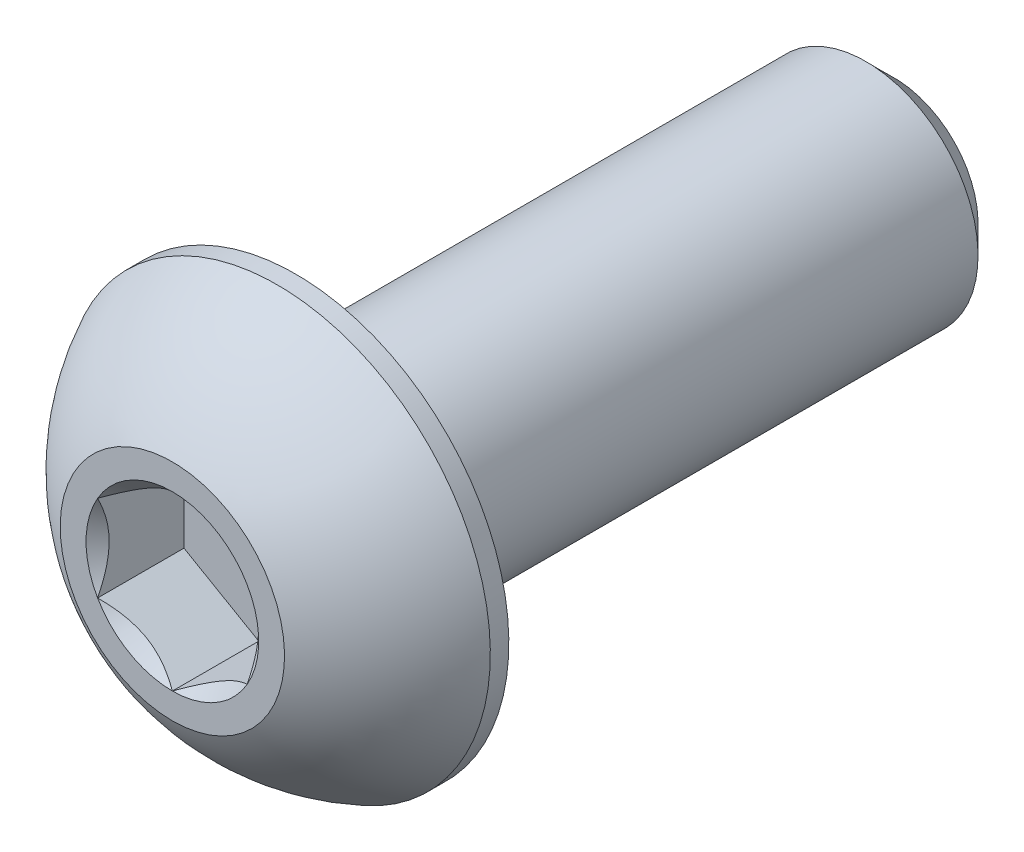
SolidWorks part; units mm, degrees
ref_plane "Front" through (0, 0, 0) normal (0, 0, 1) x (1, 0, 0)
ref_plane "Top" through (0, 0, 0) normal (0, 1, 0) x (1, 0, 0)
ref_plane "Right" through (0, 0, 0) normal (1, 0, 0) x (0, 0, -1)
sketch "Sketch1" plane through (0, 0, 0) normal (1, 0, 0) x (0, 0, -1)
  line L2 (-4, 1.5) -> (4, 1.5)
  line L3 (4, 1.5) -> (4, 0)
  line L4 (4, 0) -> (-4, 0)
  line L6 (-4.2475, 2.85) -> (-4, 2.85) construction
  line L7 (4, 1.5) -> (4, -1.5) construction
  line L8 (-5.65, 0) -> (-4, 0) construction
  line L9 (-4, 2.85) -> (-4, -2.85) construction
  line L11 (-4, 1.5) -> (-4, 0)
  line L13 (-5.65, 1) -> (-5.65, -1) construction
  line L14 (-5.65, 1) -> (-5.65, 1.5) construction
  line L15 (3.9688, 1.5541) -> (4.2188, 1.1211) construction
  line L16 (4.2188, 1.1211) -> (4.4688, 1.5541) construction
  line L17 (4.4688, 1.5541) -> (3.9688, 1.5541) construction
  line L18 (4, 1.5) -> (4.4375, 1.5) construction
  line L19 (4.2188, 1.5541) -> (4.2188, 1.5) construction
  line L20 (4.2188, 1.5) -> (4.2188, 1.1752) construction
  line L21 (4.2188, 1.1752) -> (4.2188, 1.1211) construction
  line L22 (4.1875, 1.1752) -> (4.25, 1.1752)
  line L23 (3.9844, 1.5271) -> (4.4531, 1.5271)
  line L24 (4.25, 1.1752) -> (4.4531, 1.5271)
  line L25 (4.1875, 1.1752) -> (3.9844, 1.5271)
  line L26 (3.625, 1.5) -> (4, 1.125)
  arc A3 (-5.65, 1.5) -> (-4.2475, 2.85) centre (-2.8552, 0) cw construction
  point P29 (4.2187, 1.5271)
  point P30 (2.75, -1.5)
  point P33 (0, 0)
  dimension "Thread Size" = 3
  dimension "D1" = 0.2475
  dimension "Head Height" = 1.65
  dimension "Head Diameter" = 5.7
  dimension "Length" = 8
  dimension "Drive Size" = 2
  dimension "Thread Pitch" = 0.5
  dimension "D3" = 0.0625
  dimension "D2" = 0.375
  dimension "D4" = 45
  dimension "D5" = 1.25
sketch "Sketch10" plane through (0, 0, 0) normal (1, 0, 0) x (0, 0, -1)
  line L0 (3.625, 1.5) -> (4, 1.125) construction
  line L1 (3.625, 1.5) -> (4, 1.125)
  line L4 (4, 1.5) -> (-4, 1.5)
  line L5 (4, 0) -> (4, 1.5)
  line L6 (-4, 0) -> (4, 0)
  line L7 (-4, 1.5) -> (-4, 0)
  line L8 (3.625, 1.5) -> (-4, 1.5)
  line L9 (4, 0) -> (4, 1.125)
  line L10 (-4, 0) -> (4, 0)
  line L11 (-4, 1.5) -> (-4, 0)
  dimension "D1" = 0
revolve "Revolve3" add sketch "Sketch10" angle 360 about L8
sketch "Sketch7" plane through (0, 0, 0) normal (1, 0, 0) x (0, 0, -1)
  line L6 (-4.2475, 2.85) -> (-4, 2.85) construction
  line L8 (-5.65, 0) -> (-4, 0) construction
  line L11 (-4, 2.85) -> (-4, -2.85) construction
  line L12 (-4.2475, 2.85) -> (-4, 2.85)
  line L13 (-5.65, 0) -> (-4, 0)
  line L14 (-5.65, 1) -> (-5.65, -1) construction
  line L15 (-4, 2.85) -> (-4, 0)
  line L16 (-5.65, 1.5) -> (-5.65, 0)
  arc A2 (-4.2475, 2.85) -> (-5.65, 1.5) centre (-2.8552, 0) ccw construction
  arc A3 (-4.2475, 2.85) -> (-5.65, 1.5) centre (-2.8552, 0) ccw
revolve "Revolve2" add sketch "Sketch7" angle 360 mid plane about L13
sketch "Sketch5" plane through (0, 0, 5.65) normal (0, 0, 1) x (1, 0, 0)
  line L1 (1, -0.5774) -> (1, 0.5774)
  line L2 (1, 0.5774) -> (0, 1.1547)
  line L3 (0, 1.1547) -> (-1, 0.5774)
  line L4 (-1, 0.5774) -> (-1, -0.5774)
  line L5 (-1, -0.5774) -> (0, -1.1547)
  line L6 (0, -1.1547) -> (1, -0.5774)
  circle A0 centre (0, 0) radius 1 construction
extrude "Cut-Extrude2" cut sketch "Sketch5" against normal blind 1.155
sketch "Sketch6" plane through (0, 0, 5.65) normal (0, 0, 1) x (1, 0, 0)
  circle A0 centre (0, 0) radius 1.1547
extrude "Cut-Extrude3" cut sketch "Sketch6" against normal blind 1.155 draft 45
sketch "Sketch9" [suppressed] plane through (0, 0, 4) normal (0, 0, -1) x (-1, 0, 0)
  circle A0 centre (0, 0) radius 1.5 construction
  circle A4 centre (0, 0) radius 1.5
split "Split1" [suppressed] bodies to split 113
sketch "Sketch11" [suppressed] plane through (0, 0, -4) normal (0, 0, -1) x (-1, 0, 0)
  circle A0 centre (0, 0) radius 1.5 construction
  circle A1 centre (0, 0) radius 1.5
curve "Helix/Spiral1" [suppressed] pitch 0.5 height 9.65 turns 19.3
sketch "Sketch12" [suppressed] plane through (0, 0, 0) normal (1, 0, 0) x (0, 0, -1)
  line L0 (4.1875, 1.1752) -> (4.25, 1.1752) construction
  line L1 (4.25, 1.1752) -> (4.4531, 1.5271) construction
  line L2 (3.9844, 1.5271) -> (4.4531, 1.5271) construction
  line L3 (4.1875, 1.1752) -> (3.9844, 1.5271) construction
  line L4 (4.1875, 1.1752) -> (4.25, 1.1752)
  line L5 (4.25, 1.1752) -> (4.4531, 1.5271)
  line L6 (3.9844, 1.5271) -> (4.4531, 1.5271)
  line L7 (4.1875, 1.1752) -> (3.9844, 1.5271)
sweep "Cut-Sweep2" [suppressed] cut profiles "Sketch12" path "Helix/Spiral1"
extrude "Boss-Extrude1" [suppressed] add sketch "Sketch9" along normal blind 10 draft 45
equation "\"D1@Cut-Extrude2\" = \"Head Height@Sketch1\" * .7"
equation "\"D1@Sketch1\" = \"Head Height@Sketch1\" * .15"
equation "\"D1@Cut-Extrude3\" = \"D1@Cut-Extrude2\""
equation "\"D3@Sketch1\" = \"Thread Pitch@Sketch1\" / 8"
equation "\"D2@Sketch1\" = \"Thread Pitch@Sketch1\" * 0.75"
equation "\"D3@Helix/Spiral1\" = \"Length@Sketch1\" + \"Head Height@Sketch1\""
equation "\"D4@Helix/Spiral1\" = \"Thread Pitch@Sketch1\""
equation "\"D5@Sketch1\" = \"Thread Pitch@Sketch1\" * 2.5"
